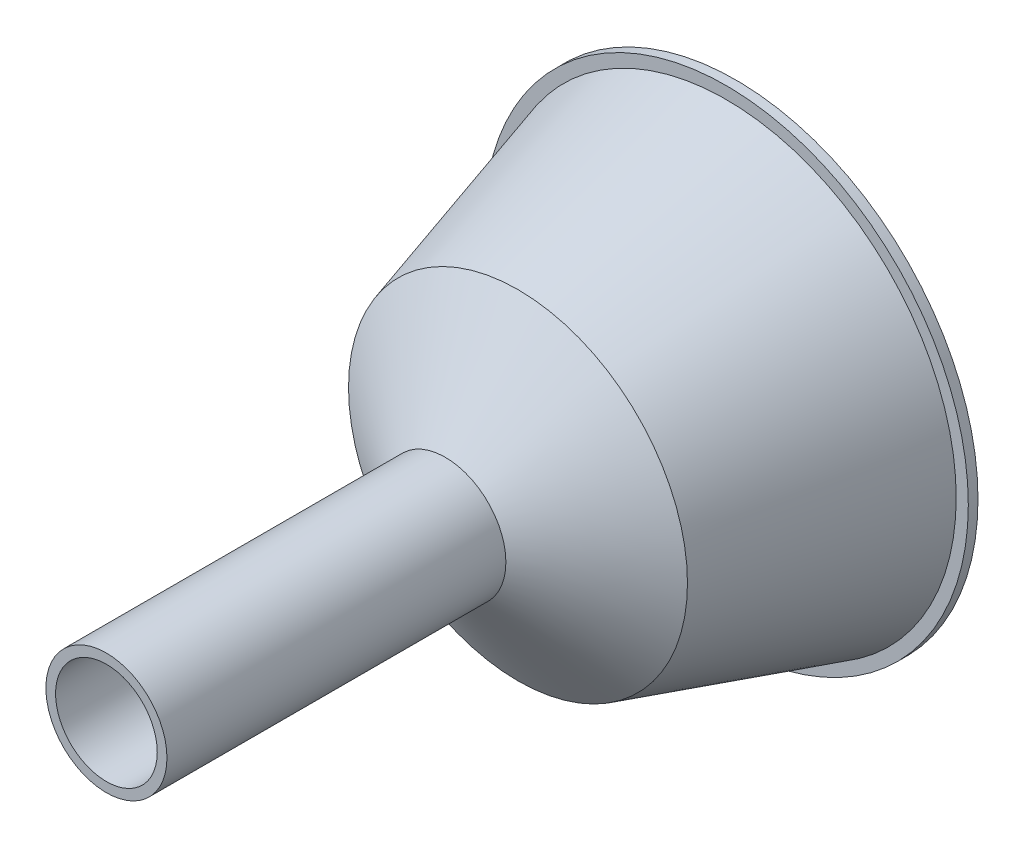
SolidWorks part; units mm, degrees
ref_plane "Alzado" through (0, 0, 0) normal (0, 0, 1) x (1, 0, 0)
ref_plane "Planta" through (0, 0, 0) normal (0, 1, 0) x (1, 0, 0)
ref_plane "Vista lateral" through (0, 0, 0) normal (1, 0, 0) x (0, 0, -1)
sketch "Croquis1" plane through (0, 0, 0) normal (0, 1, 0) x (1, 0, 0)
  line L0 (0, -65) -> (0, 65)
  line L1 (0, 65) -> (50, 65)
  line L2 (50, 65) -> (50, 63)
  line L3 (50, 63) -> (47.5, 63)
  line L4 (0, -65) -> (12.5, -65)
  line L5 (12.5, -65) -> (12.5, 5)
  line L6 (12.5, 5) -> (35, 5) construction
  line L7 (0, 20) -> (35, 20) construction
  line L8 (35, 5) -> (35, 20) construction
  line L9 (12.5, 5) -> (35, 20)
  line L10 (47.5, 63) -> (35, 20)
  point P4 (0, 0)
  dimension "D1" = 130
  dimension "D2" = 50
  dimension "D3" = 2
  dimension "D4" = 2.5
  dimension "D5" = 12.5
  dimension "D6" = 70
  dimension "D7" = 35
  dimension "D8" = 15
revolve "Revolución1" add sketch "Croquis1" angle 360 about L0
shell "Vaciado1" thickness 2 removed face at (12.5, 0, 65) removed face at (50, 0, -65)
